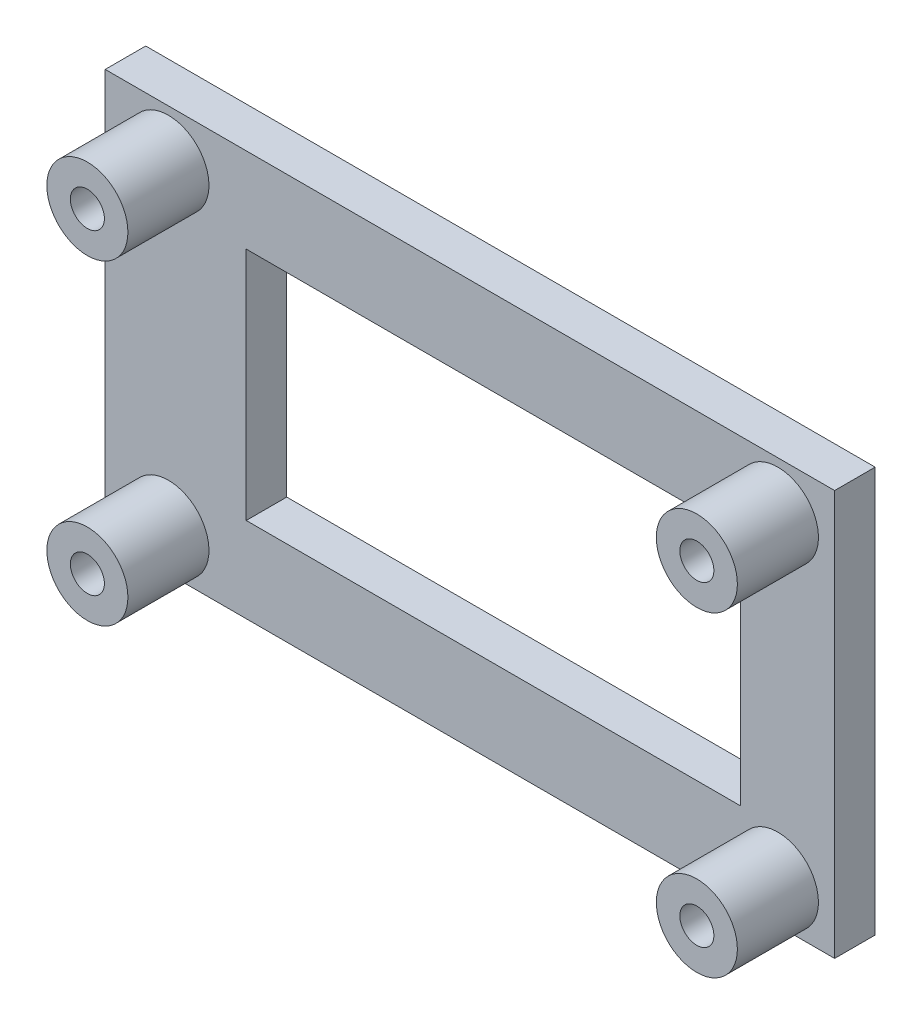
SolidWorks part; units mm, degrees
ref_plane "Front Plane" through (0, 0, 0) normal (0, 0, 1) x (1, 0, 0)
ref_plane "Top Plane" through (0, 0, 0) normal (0, 1, 0) x (1, 0, 0)
ref_plane "Right Plane" through (0, 0, 0) normal (1, 0, 0) x (0, 0, -1)
sketch "Sketch1" plane through (0, 0, 0) normal (0, 0, 1) x (1, 0, 0)
  line L1 (0, 0) -> (45, 0)
  line L2 (0, 0) -> (0, 25)
  line L3 (0, 25) -> (45, 25)
  line L4 (45, 0) -> (45, 25)
  line L5 (3.9, 22) -> (41.5, 22) construction
  line L6 (3.9, 22) -> (3.9, 2.5) construction
  line L7 (3.9, 2.5) -> (41.5, 2.5) construction
  line L8 (41.5, 22) -> (41.5, 2.5) construction
  line L9 (1.7, 24.25) -> (43.3, 24.25) construction
  line L10 (1.7, 24.25) -> (1.7, 0.75) construction
  line L11 (1.7, 0.75) -> (43.3, 0.75) construction
  line L12 (43.3, 24.25) -> (43.3, 0.75) construction
  circle A0 centre (3.9, 22) radius 2.5
  circle A1 centre (41.5, 22) radius 2.5
  circle A2 centre (41.5, 2.5) radius 2.5
  circle A3 centre (3.9, 2.5) radius 2.5
  point P10 (22.5, 0)
  point P21 (43.3, 12.5)
  point P22 (45, 12.5)
  point P23 (22.5, 0.75)
  dimension "D5" = 5
  dimension "D1" = 25
  dimension "D2" = 45
  dimension "D3" = 19.5
  dimension "D4" = 37.6
  dimension "D6" = 41.6
  dimension "D7" = 23.5
  dimension "D8" = 3.5
  dimension "D9" = 3
extrude "Boss-Extrude1" add sketch "Sketch1" against normal blind 2.5 contours L3 L4 L1 L2
extrude "Boss-Extrude2" add sketch "Sketch1<3>" along normal blind 5 contours A0 | A3 | A2 | A1 region at (3.9, 2.5, 0) region at (41.5, 2.5, 0) region at (3.9, 22, 0) region at (41.5, 22, 0)
sketch "Sketch1<3>" plane through (0, 0, 0) normal (0, 0, 1) x (1, 0, 0) same geometry as "Sketch1"
sketch "Sketch2" plane through (0, 0, 5) normal (0, 0, 1) x (1, 0, 0)
  circle A0 centre (3.9, 22) radius 1.05
  circle A1 centre (3.9, 2.5) radius 1.05
  circle A2 centre (41.5, 22) radius 1.05
  circle A3 centre (41.5, 2.5) radius 1.05
  dimension "D1" = 2.1
extrude "Cut-Extrude1" cut sketch "Sketch2" against normal blind 5
sketch "Sketch3" plane through (0, 0, 0) normal (0, 0, 1) x (1, 0, 0)
  line L1 (8.7, 19.75) -> (39.2, 19.75)
  line L2 (8.7, 19.75) -> (8.7, 5.25)
  line L3 (8.7, 5.25) -> (39.2, 5.25)
  line L4 (39.2, 19.75) -> (39.2, 5.25)
  line L7 (43.3, 24.25) -> (43.3, 0.75) construction
  line L10 (1.7, 24.25) -> (43.3, 24.25) construction
  dimension "D1" = 4.1
  dimension "D2" = 30.5
  dimension "D3" = 14.5
  dimension "D4" = 4.5
extrude "Cut-Extrude2" cut sketch "Sketch3" against normal up to surface (2.5 mm away) contours L2 L3 L4 L1 up to face at (22.5, 12.5, -2.5)
